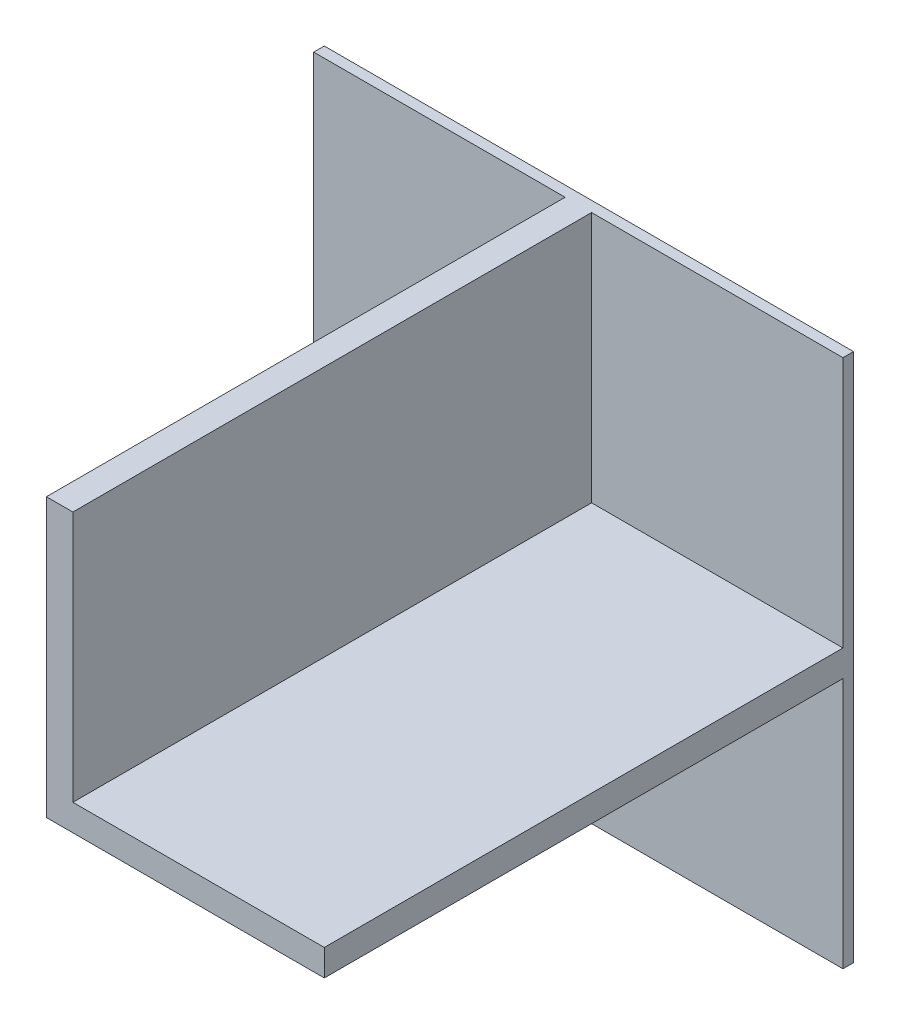
SolidWorks part; units mm, degrees
ref_plane "Płaszczyzna przednia" through (0, 0, 0) normal (0, 0, 1) x (1, 0, 0)
ref_plane "Płaszczyzna górna" through (0, 0, 0) normal (0, 1, 0) x (1, 0, 0)
ref_plane "Płaszczyzna prawa" through (0, 0, 0) normal (1, 0, 0) x (0, 0, -1)
sketch "Szkic1" plane through (0, 0, 0) normal (0, 0, 1) x (1, 0, 0)
  line L0 (0, 0) -> (100, 0)
  line L1 (0, 0) -> (-100, 0)
  line L2 (0, 0) -> (0, 100)
  line L3 (0, 0) -> (0, -100)
  line L4 (0, 100) -> (100, 100)
  line L5 (100, 100) -> (100, 0)
  line L6 (100, -100) -> (0, -100)
  line L7 (100, 0) -> (100, -100)
  line L8 (0, 100) -> (-100, 100)
  line L9 (-100, 100) -> (-100, 0)
  line L10 (-100, -100) -> (-100, 0)
  line L11 (0, -100) -> (-100, -100)
  dimension "D1" = 100
  dimension "D2" = 100
  dimension "D3" = 100
  dimension "D4" = 100
  dimension "D5" = 100
  dimension "D6" = 100
  dimension "D7" = 100
  dimension "D8" = 100
  dimension "D9" = 100
  dimension "D10" = 100
  dimension "D11" = 100
extrude "Dodanie-wyciągnięcie1" add sketch "Szkic1" along normal blind 4 contours L8 L9 L1 L2 | L5 L4 L2 L0 | L7 L0 L3 L6 | L11 L3 L1 L10 region at (50, 50, 0) region at (-50, -50, 0) region at (-50, 50, 0) region at (50, -50, 0)
sketch "Szkic2" plane through (0, 0, 4) normal (0, 0, 1) x (1, 0, 0)
  line L1 (100, 100) -> (-100, 100) construction
  line L2 (100, -100) -> (-100, -100) construction
  line L9 (-2, -100) -> (2, -100)
  line L10 (2, 100) -> (-2, 100)
  line L14 (100, 100) -> (100, -100) construction
  line L17 (100, 2) -> (100, -2)
  line L21 (0, 0) -> (-5, 0)
  line L22 (0, 0) -> (5, 0)
  line L23 (-5, 0) -> (-5, 100)
  line L24 (5, 0) -> (5, 100)
  line L25 (0, -5) -> (100, -5)
  line L26 (5, 5) -> (100, 5)
  line L27 (-5, -5) -> (-5, 0)
  line L28 (0, -5) -> (-5, -5)
  line M10 (100, -100) -> (100, 100)
  line M11 (100, 100) -> (-100, 100)
  dimension "D3" = 4
  dimension "D7" = 5
  dimension "D8" = 4
  dimension "D11" = 5
  dimension "D12" = 5
extrude "Dodanie-wyciągnięcie3" add sketch "Szkic2" along normal blind 196 contours L22 L24 L23 L21 M11 | L28 L25 L26 L24 L22 L21 L27 M10 region at (0, 50, 4) region at (49.875, -0.125, 4)
